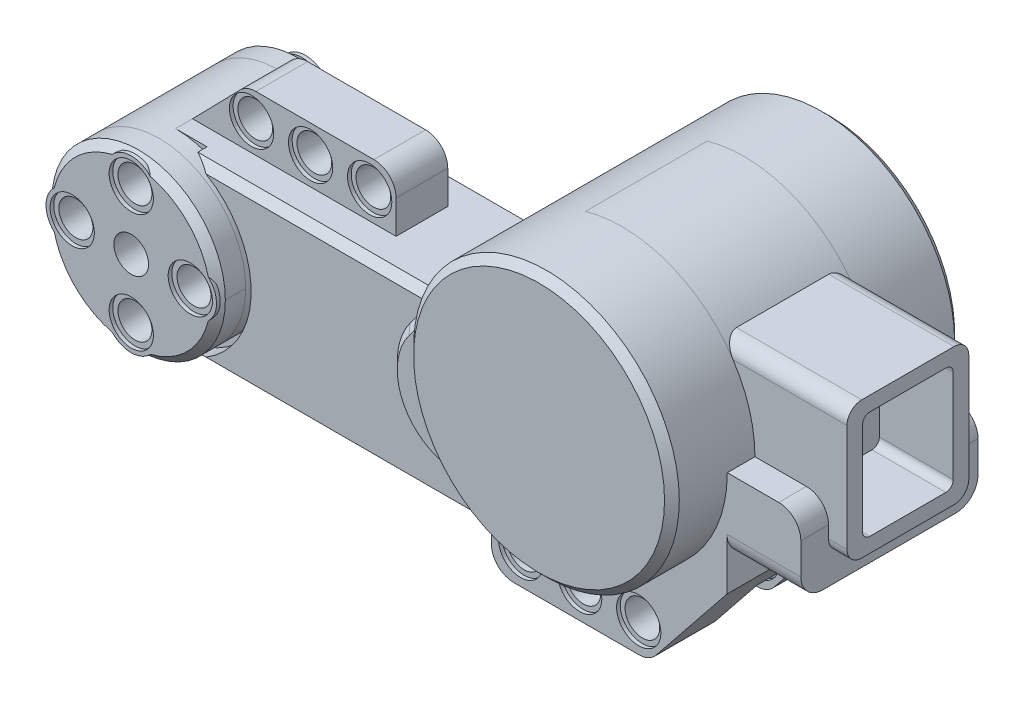
SolidWorks part; units mm, degrees
material "ABS"
ref_plane "Front Plane" through (0, 0, 0) normal (0, 0, 1) x (1, 0, 0)
ref_plane "Top Plane" through (0, 0, 0) normal (0, 1, 0) x (1, 0, 0)
ref_plane "Right Plane" through (0, 0, 0) normal (1, 0, 0) x (0, 0, -1)
sketch "Sketch1" plane through (0, 0, 0) normal (0, 0, 1) x (1, 0, 0)
  line L1 (0, 0) -> (44, 0)
  line L2 (0, 0) -> (0, 23.5) construction
  line L3 (0, 23.5) -> (44, 23.5)
  line L4 (44, 0) -> (44, 23.5)
  arc A0 (0, 23.5) -> (0, 0) centre (0, 11.75) ccw
  dimension "D1" = 44
  dimension "D2" = 23.5
extrude "Boss-Extrude1" add sketch "Sketch1" along normal blind 16.1
sketch "Sketch2" plane through (0, 0, 16.1) normal (0, 0, 1) x (1, 0, 0)
  line L0 (0, 23.5) -> (0, 0) construction
  circle A0 centre (0, 11.75) radius 12.5
  dimension "D1" = 25
extrude "Cut-Extrude1" cut sketch "Sketch2" against normal blind 2.25
sketch "Sketch3" plane through (0, 0, 0) normal (0, 0, -1) x (-1, 0, 0)
  line L2 (-4.2647, 0) -> (0, 0)
  line L3 (0, 23.5) -> (-4.2647, 23.5)
  line L4 (-4.2647, 0) -> (0, 0)
  line L5 (0, 23.5) -> (-4.2647, 23.5)
  arc A2 (-4.2647, 23.5) -> (-4.2647, 0) centre (0, 11.75) ccw
  arc A3 (0, 0) -> (0, 23.5) centre (0, 11.75) ccw
  arc A4 (-4.2647, 23.5) -> (-4.2647, 0) centre (0, 11.75) ccw
  arc A5 (0, 0) -> (0, 23.5) centre (0, 11.75) ccw
  dimension "D1" = 0
extrude "Cut-Extrude2" cut sketch "Sketch3" against normal blind 2.25
sketch "Sketch5" plane through (0, 0, 16.1) normal (0, 0, 1) x (1, 0, 0)
  line L0 (44, 0) -> (44, 23.5) construction
  line L1 (35.5, 7.5) -> (49.045, 7.5)
  line L2 (35.5, 7.5) -> (26.5, 7.5)
  line L3 (26.5, 7.5) -> (48.4991, 37.4141)
  line L4 (53, 3.45) -> (61, 3.45) construction
  line L5 (4.2647, 0) -> (44, 0) construction
  line L6 (61, 3.45) -> (69, 3.45) construction
  line L7 (49.045, 7.5) -> (49.045, -0.6)
  line L8 (49.045, -0.6) -> (76.955, -0.6) construction
  line L9 (76.955, 7.5) -> (76.955, -0.6) construction
  line L10 (70.455, -0.6) -> (76.955, 7.5)
  line L11 (76.955, 7.5) -> (80.9673, 12.5)
  line L12 (80.9673, 12.5) -> (80.9673, 16.5)
  line L13 (80.9673, 16.5) -> (90.9673, 16.5)
  line L14 (90.9673, 16.5) -> (90.9673, 26.75)
  line L15 (90.9673, 26.75) -> (81, 26.75)
  line L16 (49.045, -0.6) -> (70.455, -0.6)
  arc A0 (81, 26.75) -> (48.4991, 37.4141) centre (63, 26.75) ccw
  circle A1 centre (61, 3.45) radius 2.35
  circle A2 centre (69, 3.45) radius 2.35
  circle A3 centre (53, 3.45) radius 2.35
  point P1 (63, -0.6)
  point P21 (49.045, 3.45)
  dimension "D4" = 36
  dimension "D5" = 4.7
  dimension "D1" = 8.1
  dimension "D2" = 8.5
  dimension "D3" = 7.5
  dimension "D6" = 63
  dimension "D7" = 27.35
  dimension "D8" = 27.91
  dimension "D9" = 8
  dimension "D10" = 6.5
  dimension "D11" = 53
  dimension "D12" = 9
  dimension "D13" = 5
  dimension "D14" = 10
  dimension "D15" = 4
extrude "Boss-Extrude2" add sketch "Sketch5" against normal blind 20
sketch "Sketch6" plane through (0, 0, -3.9) normal (0, 0, -1) x (-1, 0, 0)
  circle A0 centre (-63, 26.75) radius 18
  arc A1 (-48.4991, 37.4141) -> (-81, 26.75) centre (-63, 26.75) ccw construction
extrude "Boss-Extrude3" add sketch "Sketch6" along normal blind 7.8
sketch "Sketch7" plane through (0, 0, 16.1) normal (0, 0, 1) x (1, 0, 0)
  line L9 (90.9673, 26.75) -> (81, 26.75)
  line L10 (90.9673, 16.5) -> (90.9673, 26.75)
  line L11 (80.9673, 16.5) -> (90.9673, 16.5)
  line L12 (80.9673, 12.5) -> (80.9673, 16.5)
  line L13 (70.455, -0.6) -> (80.9673, 12.5)
  line L14 (49.045, -0.6) -> (70.455, -0.6)
  line L15 (49.045, 7.5) -> (49.045, -0.6)
  line L16 (26.5, 7.5) -> (49.045, 7.5)
  line L17 (48.4991, 37.4141) -> (26.5, 7.5)
  line L18 (90.9673, 26.75) -> (81, 26.75)
  line L19 (90.9673, 16.5) -> (90.9673, 26.75)
  line L20 (80.9673, 16.5) -> (90.9673, 16.5)
  line L21 (80.9673, 12.5) -> (80.9673, 16.5)
  line L22 (70.455, -0.6) -> (80.9673, 12.5)
  line L23 (49.045, -0.6) -> (70.455, -0.6)
  line L24 (49.045, 7.5) -> (49.045, -0.6)
  line L25 (26.5, 7.5) -> (49.045, 7.5)
  line L26 (48.4991, 37.4141) -> (26.5, 7.5)
  arc A0 (81, 26.75) -> (48.4991, 37.4141) centre (63, 26.75) ccw construction
  arc A1 (48.4991, 37.4141) -> (81, 26.75) centre (63, 26.75) ccw
  circle A2 centre (69, 3.45) radius 2.35 construction
  arc A3 (81, 26.75) -> (48.4991, 37.4141) centre (63, 26.75) ccw
  circle A4 centre (61, 3.45) radius 2.35 construction
  circle A5 centre (53, 3.45) radius 2.35 construction
  circle A6 centre (69, 3.45) radius 2.35
  circle A7 centre (61, 3.45) radius 2.35
  circle A8 centre (53, 3.45) radius 2.35
  dimension "D1" = 0
extrude "Boss-Extrude4" add sketch "Sketch7" along normal blind 4
sketch "Sketch8" plane through (0, 0, 20.1) normal (0, 0, 1) x (1, 0, 0)
  circle A1 centre (63, 26.75) radius 18
  circle A2 centre (63, 26.75) radius 18
  dimension "D1" = 0
extrude "Boss-Extrude5" add sketch "Sketch8" along normal blind 7.5
fillet "Fillet1" radius 9 1 edges at (26.5, 7.5, 18.1)
fillet "Fillet2" radius 3 2 edges at (70.455, -0.6, 8.1) (49.045, -0.6, 8.1)
sketch "Sketch9" plane through (0, 0, 0) normal (0, 0, -1) x (-1, 0, 0)
  line L0 (-44, 0) -> (-49.045, 7.5)
  line L1 (-49.045, 7.5) -> (-44, 9.0487)
  line L2 (-44, 9.0487) -> (-44, 0)
extrude "Boss-Extrude6" add sketch "Sketch9" against normal up to surface (16.1 mm away) up to face at (29.291, 12.3726, 16.1)
fillet "Fillet3" radius 3 1 edges at (44, 0, 8.05)
chamfer "Chamfer1" distance 1 angle 45 16 edges at (45, 26.75, -11.7) (46.6677, 7.5, 20.1) (36.2595, 12.4373, 20.1) (42.7695, 29.6231, 20.1) (46.6677, 7.5, -3.9) (42.7695, 29.6231, -3.9) (36.2595, 12.4373, -3.9) (46.9683, 4.4128, 0) (43.8125, 0.352, 0) (23.3336, 0, 0) (21.2656, 23.5, 0) (21.2656, 23.5, 16.1) (46.9683, 4.4128, 16.1) (43.8125, 0.352, 16.1) (23.3336, 0, 16.1) (81, 26.75, 27.6)
fillet "Fillet4" radius 3 1 edges at (90.9673, 26.75, 8.1)
fillet "Fillet5" radius 3 2 edges at (85.9673, 16.5, -3.9) (85.9673, 16.5, 20.1)
sketch "Sketch10" plane through (0, -0.6, 0) normal (0, -1, 0) x (1, 0, 0)
  line L0 (44.8917, 15.1) -> (44.8917, 1) construction
  line L1 (49.045, 12.01) -> (82.1429, 12.01)
  line L2 (49.045, 12.01) -> (49.045, 4.09)
  line L3 (49.045, 4.09) -> (82.1429, 4.09)
  line L4 (82.1429, 12.01) -> (82.1429, 4.09)
  line L5 (49.045, 15.1) -> (49.045, 1) construction
  point P4 (49.045, 8.05)
  point P7 (44.8917, 8.05)
  dimension "D1" = 7.92
  dimension "D2" = 33.0979
extrude "Cut-Extrude3" cut sketch "Sketch10" against normal up to vertex up to point (49.045, 7.5, 1)
sketch "Sketch11" plane through (90.9673, 0, 0) normal (1, 0, 0) x (0, 0, -1)
  line L1 (-14.35, 20.1) -> (-1.85, 20.1)
  line L2 (-16.35, 22.1) -> (-16.35, 36.66)
  line L3 (-14.35, 38.66) -> (-1.85, 38.66)
  line L4 (0.15, 22.1) -> (0.15, 36.66)
  line L5 (0.9, 16.5) -> (-17.1, 16.5) construction
  line L6 (0.9, 16.5) -> (-17.1, 16.5) construction
  arc A0 (-16.35, 36.66) -> (-14.35, 38.66) centre (-14.35, 36.66) cw
  arc A1 (-1.85, 38.66) -> (0.15, 36.66) centre (-1.85, 36.66) cw
  arc A2 (-1.85, 20.1) -> (0.15, 22.1) centre (-1.85, 22.1) ccw
  arc A3 (-14.35, 20.1) -> (-16.35, 22.1) centre (-14.35, 22.1) cw
  point P4 (-8.1, 20.1)
  point P9 (-8.1, 16.5)
  point P12 (-16.35, 38.66)
  point P17 (0.15, 20.1)
  point P20 (-16.35, 20.1)
  dimension "D4" = 2
  dimension "D1" = 3.6
  dimension "D2" = 16.5
  dimension "D3" = 18.56
extrude "Boss-Extrude7" add sketch "Sketch11" against normal up to surface (12.941 mm away) up to face at (45, 26.75, -10.7)
sketch "Sketch12" plane through (90.9673, 0, 0) normal (1, 0, 0) x (0, 0, -1)
  line L4 (-14.35, 20.1) -> (-1.85, 20.1)
  line L5 (0.15, 22.1) -> (0.15, 36.66)
  line L6 (-1.85, 38.66) -> (-14.35, 38.66)
  line L7 (-16.35, 36.66) -> (-16.35, 22.1)
  line L8 (-14.35, 20.1) -> (-1.85, 20.1)
  line L9 (0.15, 22.1) -> (0.15, 36.66)
  line L10 (-1.85, 38.66) -> (-14.35, 38.66)
  line L11 (-16.35, 36.66) -> (-16.35, 22.1)
  arc A4 (-1.85, 20.1) -> (0.15, 22.1) centre (-1.85, 22.1) ccw
  arc A5 (0.15, 36.66) -> (-1.85, 38.66) centre (-1.85, 36.66) ccw
  arc A6 (-14.35, 38.66) -> (-16.35, 36.66) centre (-14.35, 36.66) ccw
  arc A7 (-16.35, 22.1) -> (-14.35, 20.1) centre (-14.35, 22.1) ccw
  arc A8 (-1.85, 20.1) -> (0.15, 22.1) centre (-1.85, 22.1) ccw
  arc A9 (0.15, 36.66) -> (-1.85, 38.66) centre (-1.85, 36.66) ccw
  arc A10 (-14.35, 38.66) -> (-16.35, 36.66) centre (-14.35, 36.66) ccw
  arc A11 (-16.35, 22.1) -> (-14.35, 20.1) centre (-14.35, 22.1) ccw
  dimension "D1" = 0
extrude "Boss-Extrude8" add sketch "Sketch12" along normal blind 2.5
sketch "Sketch13" plane through (93.4673, 0, 0) normal (1, 0, 0) x (0, 0, -1)
  line L0 (-14.35, 20.1) -> (-1.85, 20.1) construction
  line L1 (-14.24, 22.1) -> (-1.96, 22.1)
  line L2 (-14.24, 22.1) -> (-14.24, 36.7)
  line L3 (-14.24, 36.7) -> (-1.96, 36.7)
  line L4 (-1.96, 22.1) -> (-1.96, 36.7)
  line L5 (-14.35, 20.1) -> (-1.85, 20.1) construction
  point P6 (-8.1, 22.1)
  point P7 (-8.1, 20.1)
  dimension "D1" = 12.28
  dimension "D2" = 14.6
  dimension "D3" = 2
extrude "Cut-Extrude5" cut sketch "Sketch13" against normal blind 10
fillet "Fillet6" radius 1 4 edges at (88.4673, 22.1, 14.24) (88.4673, 36.7, 14.24) (88.4673, 22.1, 1.96) (88.4673, 36.7, 1.96)
sketch "Sketch14" plane through (0, 0, 13.85) normal (0, 0, 1) x (1, 0, 0)
  circle A0 centre (0, 11.75) radius 11.75
  dimension "D1" = 23.5
extrude "Boss-Extrude9" add sketch "Sketch14" along normal blind 6
sketch "Sketch15" plane through (0, 0, 2.25) normal (0, 0, -1) x (-1, 0, 0)
  circle A1 centre (0, 11.75) radius 11.75
  circle A2 centre (0, 11.75) radius 11.75
  dimension "D1" = 0
extrude "Boss-Extrude10" add sketch "Sketch15" along normal blind 6
chamfer "Chamfer2" distance 1 angle 45 2 edges at (11.75, 11.75, 19.85) (-11.75, 11.75, -3.75)
sketch "Sketch16" plane through (0, 0, 19.85) normal (0, 0, 1) x (1, 0, 0)
  circle A0 centre (0, 11.75) radius 2.35
  circle A1 centre (0, 11.75) radius 11.75 construction
  dimension "D1" = 4.7
extrude "Cut-Extrude6" cut sketch "Sketch16" against normal through all
sketch "Sketch17" plane through (0, 0, 19.85) normal (0, 0, 1) x (1, 0, 0)
  line L0 (0, 11.75) -> (8, 11.75) construction
  circle A0 centre (8, 11.75) radius 2.3
  circle A1 centre (0, 3.75) radius 2.3
  circle A2 centre (-8, 11.75) radius 2.3
  circle A3 centre (0, 19.75) radius 2.3
  point P13 (0, 11.75)
  dimension "D2" = 4.6
  dimension "D1" = 8
  dimension "D3" = 4
extrude "Cut-Extrude7" cut sketch "Sketch17" against normal blind 5
sketch "Sketch18" plane through (0, 0, 19.85) normal (0, 0, 1) x (1, 0, 0)
  circle A0 centre (8, 11.75) radius 3
  circle A1 centre (0, 19.75) radius 3
  circle A2 centre (-8, 11.75) radius 3
  circle A3 centre (0, 3.75) radius 3
  dimension "D1" = 6
extrude "Cut-Extrude8" cut sketch "Sketch18" against normal blind 0.5
sketch "Sketch19" plane through (0, 0, 19.85) normal (0, 0, 1) x (1, 0, 0)
  circle A2 centre (0, 19.75) radius 3.55
  circle A3 centre (0, 19.75) radius 3.55
  circle A12 centre (-8, 11.75) radius 3.55
  circle A13 centre (-8, 11.75) radius 3.55
  circle A15 centre (8, 11.75) radius 3.55
  circle A16 centre (8, 11.75) radius 3.55
  circle A17 centre (0, 3.75) radius 3 construction
  circle A18 centre (0, 3.75) radius 3.55
  circle A19 centre (0, 3.75) radius 3.55
  arc A20 (10.6602, 13.1369) -> (10.6602, 10.3631) centre (8, 11.75) ccw construction
  circle A21 centre (-8, 11.75) radius 3 construction
  circle A22 centre (0, 19.75) radius 3 construction
  circle A23 centre (0, 3.75) radius 3
  arc A24 (10.6602, 13.1369) -> (10.6602, 10.3631) centre (8, 11.75) ccw
  circle A25 centre (-8, 11.75) radius 3
  circle A26 centre (0, 19.75) radius 3
  arc A27 (10.6602, 10.3631) -> (10.6602, 13.1369) centre (8, 11.75) ccw construction
  arc A28 (10.6602, 10.3631) -> (10.6602, 13.1369) centre (8, 11.75) ccw
  dimension "D1" = 1.25
  dimension "D2" = 1.25
  dimension "D3" = 1.25
  dimension "D4" = 1.25
extrude "Boss-Extrude11" add sketch "Sketch19" against normal blind 0.5
sketch "Sketch20" plane through (0, 0, -3.75) normal (0, 0, -1) x (-1, 0, 0)
  circle A1 centre (0, 3.75) radius 3
  arc A2 (-10.6602, 10.3631) -> (-10.6602, 13.1369) centre (-8, 11.75) ccw
  arc A3 (-10.6602, 13.1369) -> (-10.6602, 10.3631) centre (-8, 11.75) ccw
  arc A4 (-10.6602, 10.3631) -> (-10.6602, 13.1369) centre (-8, 11.75) ccw
  arc A5 (-10.6602, 13.1369) -> (-10.6602, 10.3631) centre (-8, 11.75) ccw
  circle A6 centre (0, 3.75) radius 3
  circle A7 centre (0, 3.75) radius 3.55
  circle A8 centre (0, 3.75) radius 3.55
  circle A9 centre (-8, 11.75) radius 3.55
  circle A10 centre (-8, 11.75) radius 3.55
  circle A11 centre (0, 19.75) radius 3.55
  circle A12 centre (0, 19.75) radius 3.55
  circle A13 centre (0, 19.75) radius 3
  circle A14 centre (0, 19.75) radius 3
  circle A15 centre (8, 11.75) radius 3
  circle A16 centre (8, 11.75) radius 3
  circle A17 centre (8, 11.75) radius 3.55
  circle A18 centre (8, 11.75) radius 3.55
  dimension "D1" = 0
  dimension "D2" = 0
  dimension "D3" = 0
  dimension "D4" = 0
  dimension "D5" = 0
  dimension "D6" = 0
  dimension "D7" = 0
  dimension "D8" = 0
extrude "Boss-Extrude12" add sketch "Sketch20" against normal blind 0.5
sketch "Sketch21" plane through (0, 0, -3.75) normal (0, 0, -1) x (-1, 0, 0)
  circle A0 centre (0, 3.75) radius 3 construction
  circle A1 centre (8, 11.75) radius 3 construction
  circle A2 centre (-8, 11.75) radius 3 construction
  circle A3 centre (0, 19.75) radius 3 construction
  circle A4 centre (0, 3.75) radius 3
  circle A5 centre (8, 11.75) radius 3
  circle A6 centre (-8, 11.75) radius 3
  circle A7 centre (0, 19.75) radius 3
extrude "Cut-Extrude9" cut sketch "Sketch21" against normal blind 0.5
sketch "Sketch22" plane through (0, 0, -3.75) normal (0, 0, -1) x (-1, 0, 0)
  circle A0 centre (0, 3.75) radius 2.3 construction
  circle A1 centre (8, 11.75) radius 2.3 construction
  circle A2 centre (0, 19.75) radius 2.3 construction
  circle A3 centre (-8, 11.75) radius 2.3 construction
  circle A4 centre (0, 3.75) radius 2.3
  circle A5 centre (8, 11.75) radius 2.3
  circle A6 centre (0, 19.75) radius 2.3
  circle A7 centre (-8, 11.75) radius 2.3
extrude "Cut-Extrude10" cut sketch "Sketch22" against normal blind 5
ref_plane "Plane1" through (0, 0, 8.05) normal (0, 0, 1) x (1, 0, 0)
sketch "Sketch23" plane through (0, 0, 8.05) normal (0, 0, 1) x (1, 0, 0)
  line L0 (4.2647, 23.5) -> (38.2665, 23.5) construction
  line L1 (7.32, 23.5) -> (27.58, 23.5)
  line L2 (7.32, 23.5) -> (7.32, 31) construction
  line L3 (7.32, 31) -> (27.58, 31)
  line L4 (27.58, 23.5) -> (27.58, 31)
  line L5 (7.32, 31) -> (0, 23.5)
  line L6 (0, 23.5) -> (7.32, 23.5)
  line L7 (8, 27.25) -> (16, 27.25) construction
  line L8 (16, 27.25) -> (24, 27.25) construction
  circle A0 centre (8, 27.25) radius 2.35
  circle A1 centre (16, 27.25) radius 2.35
  circle A2 centre (24, 27.25) radius 2.35
  circle A3 centre (0, 11.75) radius 2.35 construction
  circle A4 centre (0, 11.75) radius 2.35 construction
  point P15 (27.58, 27.25)
  dimension "D4" = 4.7
  dimension "D1" = 27.58
  dimension "D2" = 20.26
  dimension "D3" = 7.5
  dimension "D5" = 8
  dimension "D6" = 8
extrude "Boss-Extrude13" add sketch "Sketch23" along normal blind 3.5
sketch "Sketch24" plane through (0, 0, 8.05) normal (0, 0, -1) x (-1, 0, 0)
  line L4 (-27.58, 23.5) -> (0, 23.5)
  line L5 (0, 23.5) -> (-7.32, 31)
  line L6 (-7.32, 31) -> (-27.58, 31)
  line L7 (-27.58, 31) -> (-27.58, 23.5)
  line L8 (-27.58, 23.5) -> (0, 23.5)
  line L9 (0, 23.5) -> (-7.32, 31)
  line L10 (-7.32, 31) -> (-27.58, 31)
  line L11 (-27.58, 31) -> (-27.58, 23.5)
  circle A0 centre (-8, 27.25) radius 2.35 construction
  circle A1 centre (-16, 27.25) radius 2.35 construction
  circle A2 centre (-24, 27.25) radius 2.35 construction
  circle A3 centre (-8, 27.25) radius 2.35
  circle A4 centre (-16, 27.25) radius 2.35
  circle A5 centre (-24, 27.25) radius 2.35
  dimension "D1" = 0
extrude "Boss-Extrude14" add sketch "Sketch24" along normal blind 3.5
sketch "Sketch25" plane through (0, 0, 11.55) normal (0, 0, 1) x (1, 0, 0)
  circle A0 centre (16, 27.25) radius 3
  circle A1 centre (24, 27.25) radius 3
  circle A2 centre (8, 27.25) radius 3
  dimension "D1" = 6
extrude "Cut-Extrude11" cut sketch "Sketch25" against normal blind 0.5
sketch "Sketch26" plane through (0, 0, 4.55) normal (0, 0, -1) x (-1, 0, 0)
  circle A0 centre (-24, 27.25) radius 3 construction
  circle A1 centre (-16, 27.25) radius 3 construction
  circle A2 centre (-8, 27.25) radius 3 construction
  circle A3 centre (-24, 27.25) radius 3
  circle A4 centre (-16, 27.25) radius 3
  circle A5 centre (-8, 27.25) radius 3
extrude "Cut-Extrude12" cut sketch "Sketch26" against normal blind 0.5
fillet "Fillet7" radius 3 2 edges at (27.58, 31, 8.05) (7.32, 31, 8.05)
sketch "Sketch27" plane through (0, 0, 20.1) normal (0, 0, 1) x (1, 0, 0)
  circle A0 centre (53, 3.45) radius 3
  circle A1 centre (61, 3.45) radius 3
  circle A2 centre (69, 3.45) radius 3
  dimension "D1" = 6
extrude "Cut-Extrude13" cut sketch "Sketch27" against normal blind 0.5
sketch "Sketch28" plane through (0, 0, 12.01) normal (0, 0, -1) x (-1, 0, 0)
  circle A0 centre (-69, 3.45) radius 3 construction
  circle A1 centre (-61, 3.45) radius 3 construction
  circle A2 centre (-53, 3.45) radius 3 construction
  circle A3 centre (-69, 3.45) radius 3
  circle A4 centre (-61, 3.45) radius 3
  circle A5 centre (-53, 3.45) radius 3
extrude "Cut-Extrude14" cut sketch "Sketch28" against normal blind 0.5
sketch "Sketch29" plane through (0, 0, 4.09) normal (0, 0, 1) x (1, 0, 0)
  circle A0 centre (69, 3.45) radius 3 construction
  circle A1 centre (61, 3.45) radius 3 construction
  circle A2 centre (53, 3.45) radius 3 construction
  circle A3 centre (69, 3.45) radius 3
  circle A4 centre (61, 3.45) radius 3
  circle A5 centre (53, 3.45) radius 3
extrude "Cut-Extrude15" cut sketch "Sketch29" against normal blind 0.5
sketch "Sketch30" plane through (0, 0, -3.9) normal (0, 0, -1) x (-1, 0, 0)
  circle A0 centre (-53, 3.45) radius 3 construction
  circle A1 centre (-61, 3.45) radius 3 construction
  circle A2 centre (-69, 3.45) radius 3 construction
  circle A3 centre (-53, 3.45) radius 3
  circle A4 centre (-61, 3.45) radius 3
  circle A5 centre (-69, 3.45) radius 3
extrude "Cut-Extrude16" cut sketch "Sketch30" against normal blind 0.5
ref_plane "Plane2" through (0, 48.66, 0) normal (0, 1, 0) x (1, 0, 0)
sketch "Sketch31" plane through (0, 48.66, 0) normal (0, 1, 0) x (1, 0, 0)
  line L1 (78.0264, 0.15) -> (58.0264, 0.15)
  line L2 (78.0264, 0.15) -> (78.0264, -16.35)
  line L3 (78.0264, -16.35) -> (58.0264, -16.35)
  line L4 (58.0264, 0.15) -> (58.0264, -16.35)
  point P5 (78.0264, -15.1005)
  dimension "D1" = 20
split line "Split Line1"
sketch "Sketch32" plane through (0, 23.5, 0) normal (0, 1, 0) x (1, 0, 0)
  line L0 (6.3787, 0) -> (37.5311, 0) construction
  line L1 (11.75, 2.75) -> (-12.0353, 2.75)
  line L2 (11.75, 2.75) -> (11.75, 0)
  line L3 (11.75, 0) -> (-12.0353, 0)
  line L4 (-12.0353, 2.75) -> (-12.0353, 0)
  line L5 (37.5311, -16.1) -> (6.3787, -16.1) construction
  line L6 (11.75, -18.85) -> (-11.75, -18.85)
  line L7 (11.75, -18.85) -> (11.75, -16.1)
  line L8 (11.75, -16.1) -> (-11.75, -16.1)
  line L9 (-11.75, -18.85) -> (-11.75, -16.1)
  line L10 (-11.75, 2.75) -> (-11.75, -18.85) construction
  point P5 (11.75, -16.1)
  point P15 (-11.75, -16.1)
  point P18 (-13.5403, 0)
  point P19 (-13.896, 2.75)
  point P20 (-12.0353, 2.75)
split line "Split Line2"
